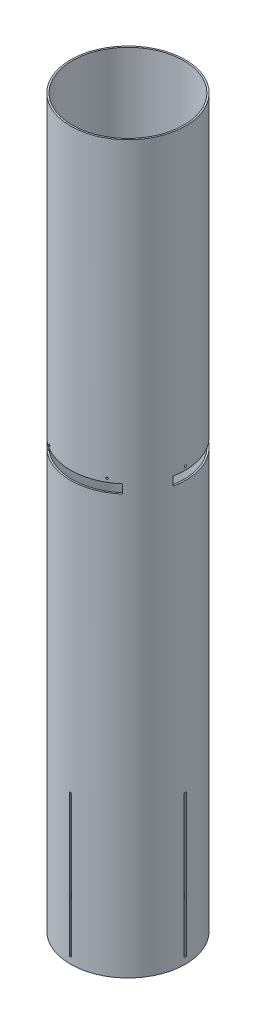
SolidWorks part; units mm, degrees
material "A-Glass Fiber"
ref_plane "Front Plane" through (0, 0, 0) normal (0, 0, 1) x (1, 0, 0)
ref_plane "Top Plane" through (0, 0, 0) normal (0, 1, 0) x (1, 0, 0)
ref_plane "Right Plane" through (0, 0, 0) normal (1, 0, 0) x (0, 0, -1)
sketch "Sketch1" plane through (0, 0, 0) normal (0, 1, 0) x (1, 0, 0)
  circle A0 centre (0, 0) radius 76.2
  circle A1 centre (0, 0) radius 78.359
  dimension "D1" = 152.4
  dimension "D2" = 156.718
extrude "Boss-Extrude1" add sketch "Sketch1" along normal blind 990.6
ref_plane "Plane1" through (0, 0, 0) normal (0.7071, 0, 0.7071) x (0.7071, 0, -0.7071)
ref_axis "Axis1" through (0, 990.6, 0) along (0, -1, 0)
sketch "Sketch2" plane through (0, 0, 0) normal (1, 0, 0) x (0, 0, -1)
  line L0 (0, 0) -> (0, 8.89)
  line L1 (1.5875, 8.89) -> (-1.5875, 8.89)
  line L2 (1.5875, 8.89) -> (1.5875, 203.2)
  line L3 (1.5875, 203.2) -> (-1.5875, 203.2)
  line L4 (-1.5875, 8.89) -> (-1.5875, 203.2)
  line L5 (1.5875, 8.89) -> (-1.5875, 203.2) construction
  line L6 (1.5875, 203.2) -> (-1.5875, 8.89) construction
  line L7 (78.359, 990.6) -> (-78.359, 990.6) construction
  line L8 (78.359, 990.6) -> (-78.359, 990.6)
  line L9 (0, 990.6) -> (0, 588.645)
  line L10 (-78.359, 0) -> (78.359, 0) construction
  circle A0 centre (0, 588.645) radius 1.3525
  point P0 (0, 106.045)
  dimension "D4" = 2.7051
  dimension "D1" = 3.175
  dimension "D2" = 194.31
  dimension "D5" = 588.645
  dimension "D3" = 203.2
extrude "Cut-Extrude1" cut sketch "Sketch2" against normal through all contours L4 L1 L2 L3 region at (0, 106.045, 0)
pattern_circular "CirPattern1" count 4 over 360 about axis through (0, 0, 0) along (0, 1, 0) of "Cut-Extrude1" reverse direction yes
extrude "Cut-Extrude2" cut sketch "Sketch2<3>" against normal through all contours A0 region at (0, 587.7157, 0.9293)
sketch "Sketch2<3>" plane through (0, 0, 0) normal (1, 0, 0) x (0, 0, -1) same geometry as "Sketch2"
pattern_circular "CirPattern2" count 6 over 360 about axis through (0, 990.6, 0) along (0, -1, 0) of "Cut-Extrude2"
sketch "Sketch3" plane through (0, 0, 0) normal (0.7071, 0, 0.7071) x (0.7071, 0, -0.7071)
  line L0 (0, 0) -> (0, 127) construction
  circle A0 centre (0, 127) radius 3.175
  dimension "D1" = 6.35
  dimension "D2" = 127
extrude "Cut-Extrude3" cut sketch "Sketch3" against normal through all
ref_plane "Plane3" through (0, 583.8825, 0) normal (0, 1, 0) x (1, 0, 0)
sketch "Sketch7" plane through (0, 583.8825, 0) normal (0, 1, 0) x (1, 0, 0)
  line L0 (0, 0) -> (-76.8534, -15.2871)
  line L1 (0, 0) -> (0, 93.232) construction
  line L2 (0, 0) -> (-25.1877, 74.2005)
  line L3 (-78.359, 0) -> (0, 0) construction
  arc A0 (-78.3473, 1.3526) -> (-78.3473, -1.3525) centre (0, 0) ccw construction
  circle A1 centre (0, 0) radius 76.2 construction
  circle A2 centre (0, 0) radius 78.359
  circle A3 centre (0, 0) radius 78.359
  circle A4 centre (0, 0) radius 76.2
  circle A5 centre (0, 0) radius 78.359 construction
  arc A6 (-38.0023, 68.527) -> (-40.345, 67.1745) centre (0, 0) ccw construction
  arc A7 (-78.3473, 1.3526) -> (-78.3473, -1.3525) centre (0, 0) ccw
  arc A8 (-38.0023, 68.527) -> (-40.345, 67.1745) centre (0, 0) ccw
  dimension "D1" = 82.5
  dimension "D3" = 11.25
  dimension "D2" = 0
extrude "Cut-Extrude4" cut sketch "Sketch7" against normal blind 12.065 contours A4 A3 L0 region at (-75.9984, 583.8825, 14.0521)
pattern_circular "CirPattern3" count 3 over 360 about axis through (0, 990.6, 0) along (0, -1, 0) of "Cut-Extrude4"
equation "\"D1@Boss-Extrude1\" = \"Aft_Section_Length\""
equation "\"AB_Coupler_OD_Length\"= 1in"
equation "\"AB_Coupling_Section_Length\"= 0.375in"
equation "\"AB_Coupler_Length\"= \"AB_Coupler_OD_Length\" + \"AB_Coupling_Section_Length\" * 2"
equation "\"AB_Coupler_Num_Screws\"= 6"
equation "\"AB_Coupling_Screw_Diameter\"= 0.1065in"
equation "\"Aft_Section_Length\"= 39in"
equation "\"D4@Sketch2\"=\"AB_Coupling_Screw_Diameter\""
equation "\"D1@CirPattern2\"=\"AB_Coupler_Num_Screws\""
equation "\"Rail_Nut_From_Bottom\"= 5in"
equation "\"Rail_Nut_Diam\"= 0.25in"
equation "\"D1@Sketch3\"=\"Rail_Nut_Diam\""
equation "\"D2@Sketch3\"=\"Rail_Nut_From_Bottom\""
equation "\"AB_BKHD_Thickness\"= 0.375in"
equation "\"AB_Mount_From_Bottom\"= 23.175in"
equation "\"Cutout_Angle\"=80"
